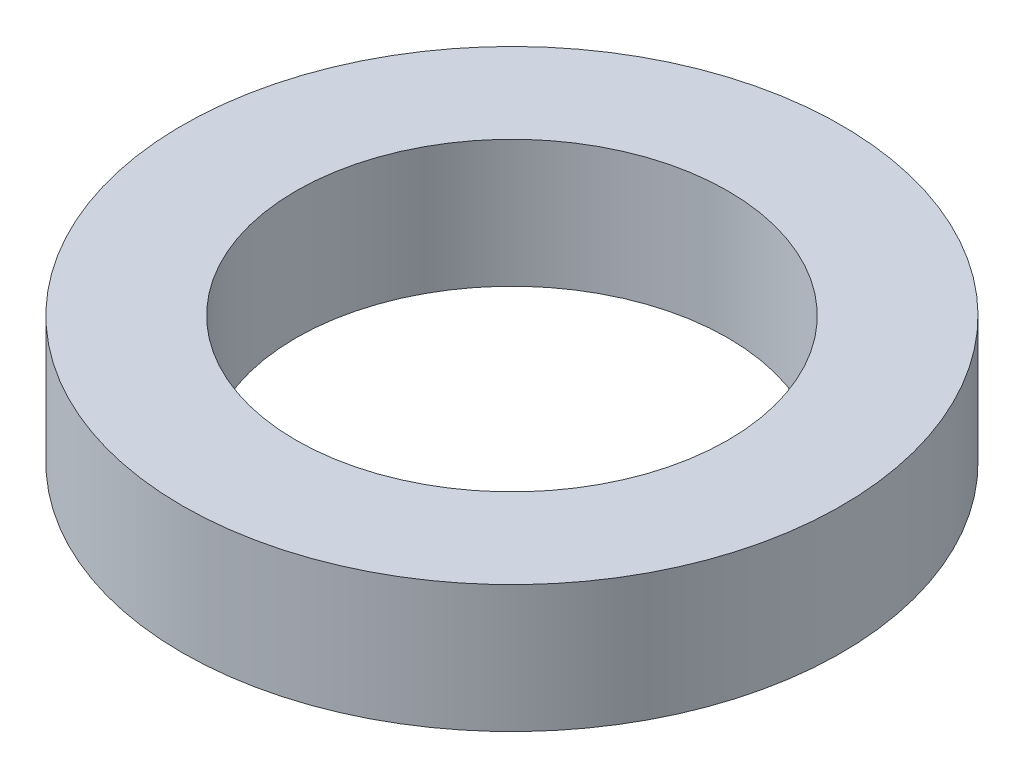
SolidWorks part; units mm, degrees
ref_plane "Front Plane" through (0, 0, 0) normal (0, 0, 1) x (1, 0, 0)
ref_plane "Top Plane" through (0, 0, 0) normal (0, 1, 0) x (1, 0, 0)
ref_plane "Right Plane" through (0, 0, 0) normal (1, 0, 0) x (0, 0, -1)
sketch "Sketch1" plane through (0, 0, 0) normal (0, 1, 0) x (1, 0, 0)
  circle A0 centre (0, 0) radius 72.5
  dimension "FLANGE_OD" = 145
extrude "Boss-Extrude1" add sketch "Sketch1" along normal blind 28
sketch "Sketch2" plane through (0, 0, 0) normal (0, 1, 0) x (1, 0, 0)
  circle A0 centre (0, 0) radius 47.5
  dimension "BORE_D" = 95
extrude "Cut-Extrude1" cut sketch "Sketch2" along normal through all
sketch "Sketch3" plane through (0, 28, 0) normal (0, 1, 0) x (1, 0, 0)
  circle A0 centre (0, 0) radius 27.552 construction
  circle A1 centre (-27.552, 0) radius 3.2718
  dimension "BOLT_D" = 6.5436
  dimension "BOLT_PCD" = 55.104
extrude "Cut-Extrude2" cut sketch "Sketch3" against normal blind 21.82 rebuild error yes
pattern_circular "CirPattern1" count 8 over 360 rebuild error yes
